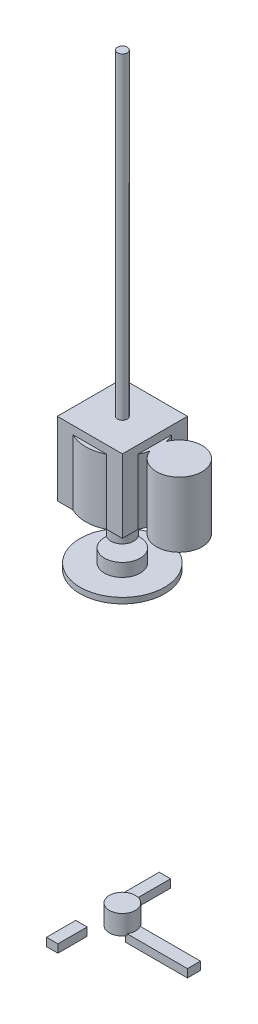
SolidWorks part; units mm, degrees
ref_plane "Front Plane" through (0, 0, 0) normal (0, 0, 1) x (1, 0, 0)
ref_plane "Top Plane" through (0, 0, 0) normal (0, 1, 0) x (1, 0, 0)
ref_plane "Right Plane" through (0, 0, 0) normal (1, 0, 0) x (0, 0, -1)
other "Configuration Table"
sketch "Sketch1" plane through (0, 0, 0) normal (0, 1, 0) x (1, 0, 0)
  line L1 (-200, -200) -> (200, -200)
  line L2 (-200, -200) -> (-200, 200)
  line L3 (-200, 200) -> (200, 200)
  line L4 (200, -200) -> (200, 200)
extrude "Boss-Extrude1" add sketch "Sketch1" along normal blind 450
sketch "Sketch2" plane through (0, 0, 0) normal (0, 1, 0) x (1, 0, 0)
  circle A0 centre (350, 0) radius 140
extrude "Boss-Extrude2" add sketch "Sketch2" along normal blind 400
sketch "Sketch3" plane through (0, 0, 0) normal (0, 1, 0) x (1, 0, 0)
  circle A0 centre (0, 0) radius 225
extrude "Boss-Extrude3" add sketch "Sketch3" along normal blind 400 flip side to cut
sketch "Sketch4" plane through (0, 0, 0) normal (0, 1, 0) x (1, 0, 0)
  circle A0 centre (0, 0) radius 260
extrude "Boss-Extrude4" add sketch "Sketch4" along normal blind 35 from offset 365 flip side to cut offset against normal yes
sketch "Sketch5" plane through (0, 0, 0) normal (0, 1, 0) x (1, 0, 0)
  circle A0 centre (0, 0) radius 110
extrude "Boss-Extrude5" add sketch "Sketch5" along normal blind 150 from offset 400 flip side to cut offset against normal yes
sketch "Sketch6" plane through (0, 0, 0) normal (0, 1, 0) x (1, 0, 0)
  circle A0 centre (0, 0) radius 70
extrude "Boss-Extrude6" add sketch "Sketch6" along normal blind 180 from offset 180 flip side to cut offset against normal yes
sketch "Sketch7" plane through (0, 0, 0) normal (0, 1, 0) x (1, 0, 0)
  circle A0 centre (0, 0) radius 30
extrude "Boss-Extrude7" add sketch "Sketch7" along normal blind 2400 flip side to cut
sketch "Sketch8" plane through (0, 0, 0) normal (0, 1, 0) x (1, 0, 0)
  circle A0 centre (0, 0) radius 80
extrude "Boss-Extrude8" add sketch "Sketch8" along normal blind 120 from offset 2260 flip side to cut offset against normal yes
sketch "Sketch9" plane through (0, 0, 0) normal (0, 1, 0) x (1, 0, 0)
  line L1 (60, -40) -> (440, -40)
  line L2 (60, -40) -> (60, 40)
  line L3 (60, 40) -> (440, 40)
  line L4 (440, -40) -> (440, 40)
  line L5 (-90, 46.6025) -> (-160, 46.6025)
  line L6 (-90, 46.6025) -> (-90, 386.4102)
  line L7 (-90, 386.4102) -> (-160, 386.4102)
  line L8 (-160, 46.6025) -> (-160, 386.4102)
  line L9 (-90, -126.6025) -> (-160, -126.6025)
  line L10 (-90, -126.6025) -> (-90, -306.4102)
  line L11 (-90, -306.4102) -> (-160, -306.4102)
  line L12 (-160, -126.6025) -> (-160, -306.4102)
extrude "Boss-Extrude9" add sketch "Sketch9" along normal blind 50 from offset 2300 flip side to cut offset against normal yes
